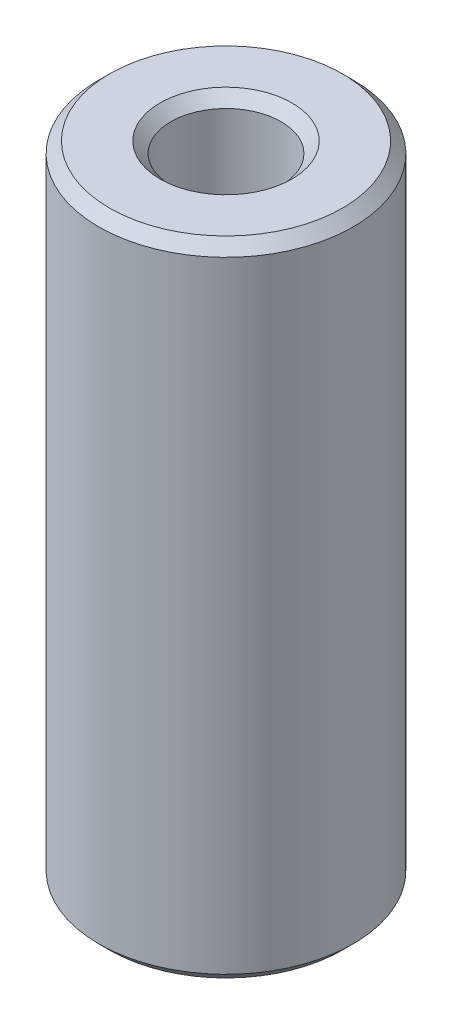
SolidWorks part; units mm, degrees
ref_plane "Front Plane" through (0, 0, 0) normal (0, 0, 1) x (1, 0, 0)
ref_plane "Top Plane" through (0, 0, 0) normal (0, 1, 0) x (1, 0, 0)
ref_plane "Right Plane" through (0, 0, 0) normal (1, 0, 0) x (0, 0, -1)
sketch "Sketch1" plane through (0, 0, 0) normal (0, 1, 0) x (1, 0, 0)
  circle A0 centre (0, 0) radius 17.5
  dimension "SLEEVE_OD" = 35
extrude "Boss-Extrude1" add sketch "Sketch1" along normal blind 88.3907
sketch "Sketch2" plane through (0, 0, 0) normal (0, 1, 0) x (1, 0, 0)
  circle A0 centre (0, 0) radius 7.5833
  dimension "BORE_D" = 15.1667
extrude "Cut-Extrude1" cut sketch "Sketch2" along normal through all
chamfer "Chamfer1" distance 1.4893 angle 45 4 edges at (0, 88.3907, 7.5833) (0, 0, 7.5833) (0, 0, 17.5) (0, 88.3907, 17.5)
